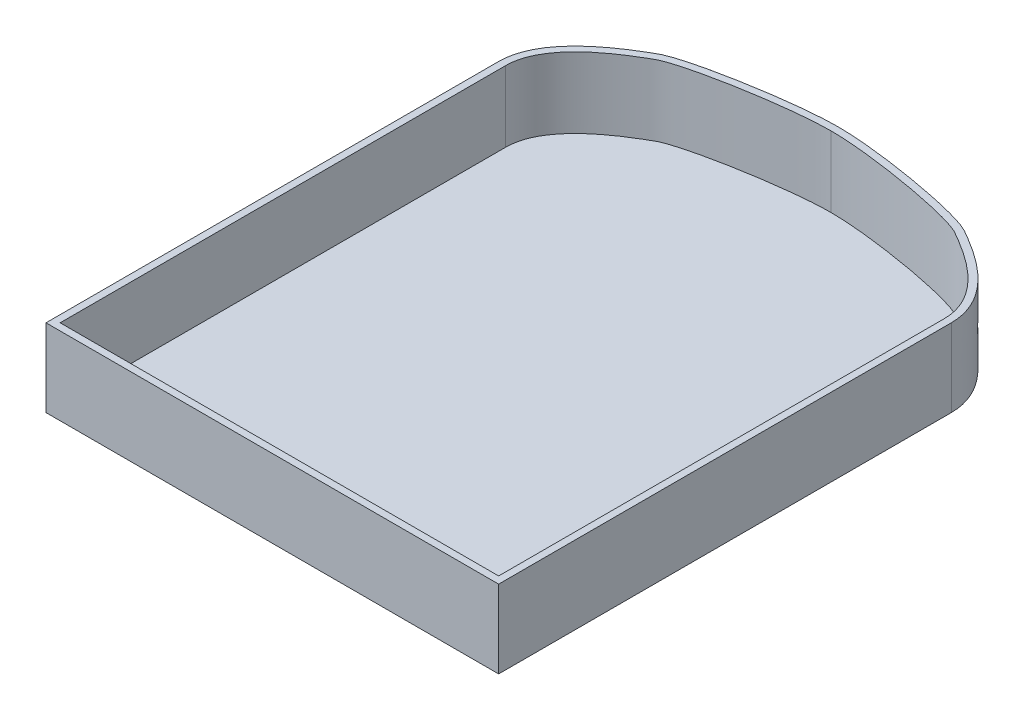
SolidWorks part; units mm, degrees
material "ABS"
ref_plane "Front Plane" through (0, 0, 0) normal (0, 0, 1) x (1, 0, 0)
ref_plane "Top Plane" through (0, 0, 0) normal (0, 1, 0) x (1, 0, 0)
ref_plane "Right Plane" through (0, 0, 0) normal (1, 0, 0) x (0, 0, -1)
sketch "Sketch1" plane through (0, 0, 0) normal (0, 1, 0) x (1, 0, 0)
  line L0 (-55, -80) -> (-55, 110) construction
  line L1 (80, 80) -> (80, -80)
  line L2 (-80, 80) -> (-80, -80)
  line L3 (-80, -80) -> (80, -80)
  line L4 (13.4478, 120) -> (-13.4478, 120) construction
  line L5 (-80, 80) -> (0, 0) construction
  line L6 (-80, -80) -> (0, 0) construction
  line L7 (140.1696, 222.6812) -> (-250.1696, -2.6812) construction
  line L8 (0, -80) -> (0, 120) construction
  spline S0 degree 3 poles (-80, 80) (-80, 95) (-57.9586, 108.2094) (-48.3668, 114.0523) (-15, 120) (0, 120) knots 0 0 0 0 0.16612 0.217304 0.51184 0.51184 0.51184 0.51184
  spline S1 degree 3 poles (80, 80) (80, 95) (57.9586, 108.2094) (48.3668, 114.0523) (15, 120) (0, 120) knots 0 0 0 0 0.16612 0.217304 0.51184 0.51184 0.51184 0.51184
  point P0 (0, 0)
  dimension "D3" = 25
  dimension "D6" = 113.1371
  dimension "D7" = 50
  dimension "D8" = 30
  dimension "D9" = 50
  dimension "D10" = 50
  dimension "D1" = 200
  dimension "D2" = 160
  dimension "D4" = 190
  dimension "D5" = 80
extrude "Boss-Extrude1" add sketch "Sketch1" along normal blind 2.5
sketch "Sketch3" plane through (0, 2.5, 0) normal (0, 1, 0) x (1, 0, 0)
  line L6 (-80, 80) -> (-80, -80)
  line L7 (-80, -80) -> (80, -80)
  line L8 (80, -80) -> (80, 80)
  line L9 (-80, 80) -> (-80, -80)
  line L10 (-80, -80) -> (80, -80)
  line L11 (80, -80) -> (80, 80)
  line L15 (-77.5, 80) -> (-77.5, -77.5)
  line L16 (-77.5, -77.5) -> (77.5, -77.5)
  line L17 (77.5, -77.5) -> (77.5, 80)
  line L18 (-77.5, 80) -> (-77.5, -77.5)
  line L19 (-77.5, -77.5) -> (77.5, -77.5)
  line L20 (77.5, -77.5) -> (77.5, 80)
  spline S4 degree 3 poles (-2906.9642, -618.3484) (562.0344, 187.5767) (-25.3353, 128.0822) (-71.1238, 100.1896) (-410.3236, -102.5425) (2892.7092, -269.8611) knots -1.229014 -1.229014 -1.229014 -1.229014 0.294536 0.34572 1.214364 1.214364 1.214364 1.214364 only from (0, 120) to (-80, 80)
  spline S5 degree 3 poles (-2892.5628, -269.8537) (410.3141, -102.5368) (71.1236, 100.1898) (25.3353, 128.0822) (-562.0328, 187.5765) (2906.9501, -618.3451) knots -0.702511 -0.702511 -0.702511 -0.702511 0.16612 0.217304 1.740852 1.740852 1.740852 1.740852 only from (80, 80) to (0, 120)
  spline S6 degree 3 poles (0, 120) (-15, 120) (-48.3668, 114.0523) (-57.9586, 108.2094) (-80, 95) (-80, 80) knots 0 0 0 0 0.294536 0.34572 0.51184 0.51184 0.51184 0.51184
  spline S7 degree 3 poles (80, 80) (80, 95) (57.9586, 108.2094) (48.3668, 114.0523) (15, 120) (0, 120) knots 0 0 0 0 0.16612 0.217304 0.51184 0.51184 0.51184 0.51184
  spline S10 degree 3 poles (649.7116, -2806.5157) (157.7684, 63.7543) (71.3763, 122.2374) (-7.815, 117.1661) (-9.7566, 116.9982) (-15.5689, 116.4083) (-19.4274, 115.902) (-27.1218, 114.7318) (-30.9575, 114.0669) (-36.6913, 112.933) (-38.5993, 112.5319) (-41.4543, 111.8826) (-42.4048, 111.6582) (-44.3029, 111.1884) (-45.2518, 110.9429) (-47.1348, 110.4247) (-48.0697, 110.1524) (-49.4545, 109.7092) (-49.9131, 109.5556) (-50.8213, 109.2304) (-51.271, 109.0591) (-52.1534, 108.6827) (-52.5848, 108.475) (-53.4295, 108.0238) (-53.8441, 107.7827) (-54.6696, 107.2932) (-55.0804, 107.0448) (-55.9027, 106.5489) (-56.3138, 106.3011) (-58.3647, 105.0521) (-59.9884, 104.0191) (-62.3722, 102.3669) (-63.1599, 101.7986) (-64.7045, 100.6307) (-65.4621, 100.0307) (-67.6842, 98.1751) (-69.0988, 96.8649) (-70.7492, 95.0983) (-71.0733, 94.7385) (-71.7083, 94.0043) (-72.0197, 93.6292) (-72.9258, 92.4878) (-73.4933, 91.7042) (-74.542, 90.0837) (-75.0233, 89.2467) (-75.8813, 87.5082) (-76.2591, 86.6008) (-97.5238, 22.5321) (214.1588, -109.4964) (2812.1935, -714.9326) knots -2.416048 -2.416048 -2.416048 -2.416048 0.0625 0.0625 0.125 0.125 0.25 0.25 0.375 0.375 0.4375 0.4375 0.46875 0.46875 0.5 0.5 0.53125 0.53125 0.546875 0.546875 0.5625 0.5625 0.578125 0.578125 0.59375 0.59375 0.609375 0.609375 0.625 0.625 0.6875 0.6875 0.71875 0.71875 0.75 0.75 0.8125 0.8125 0.828125 0.828125 0.84375 0.84375 0.875 0.875 0.90625 0.90625 0.9375 0.9375 3.090377 3.090377 3.090377 3.090377 only from (0, 117.5) to (-77.5, 80)
  spline S11 degree 3 poles (-2820.6032, -683.8631) (-228.4731, -110.921) (98.0659, 21.2534) (76.3991, 86.1764) (76.2263, 86.6364) (75.8509, 87.5394) (75.6485, 87.9819) (75.0021, 89.2855) (74.5187, 90.1226) (73.4656, 91.7439) (72.8957, 92.5281) (71.9857, 93.6707) (71.6726, 94.0466) (71.0345, 94.7821) (70.7089, 95.1424) (69.0523, 96.9103) (67.6355, 98.2186) (64.6735, 100.6864) (63.1276, 101.845) (60.7367, 103.4996) (59.9269, 104.0375) (58.2971, 105.0844) (57.4757, 105.5941) (56.2381, 106.3469) (55.8247, 106.5959) (54.9981, 107.0944) (54.585, 107.3441) (53.7547, 107.8347) (53.3375, 108.0757) (52.4873, 108.5236) (52.0531, 108.7283) (51.1672, 109.0998) (50.7166, 109.2693) (49.8075, 109.5916) (49.3489, 109.7439) (47.965, 110.1837) (47.0317, 110.4541) (45.153, 110.9689) (44.2064, 111.213) (42.3122, 111.6803) (41.3636, 111.9037) (38.5144, 112.5501) (36.6105, 112.9496) (30.8887, 114.0791) (27.0613, 114.7417) (19.3836, 115.9079) (15.5336, 116.4124) (9.7342, 117.0002) (7.797, 117.1675) (-71.3703, 122.2287) (-157.6885, 63.6621) (-646.7564, -2807.2372) knots -2.119433 -2.119433 -2.119433 -2.119433 0.0625 0.0625 0.078125 0.078125 0.09375 0.09375 0.125 0.125 0.15625 0.15625 0.171875 0.171875 0.1875 0.1875 0.25 0.25 0.3125 0.3125 0.34375 0.34375 0.375 0.375 0.390625 0.390625 0.40625 0.40625 0.421875 0.421875 0.4375 0.4375 0.453125 0.453125 0.46875 0.46875 0.5 0.5 0.53125 0.53125 0.5625 0.5625 0.625 0.625 0.75 0.75 0.875 0.875 0.9375 0.9375 3.421069 3.421069 3.421069 3.421069 only from (77.5, 80) to (0, 117.5)
  spline S12 degree 3 poles (0, 117.5) (-1.9658, 117.5) (-3.9194, 117.4156) (-7.815, 117.1661) (-9.7566, 116.9982) (-15.5689, 116.4083) (-19.4274, 115.902) (-27.1218, 114.7318) (-30.9575, 114.0669) (-36.6913, 112.933) (-38.5993, 112.5319) (-41.4543, 111.8826) (-42.4048, 111.6582) (-44.3029, 111.1884) (-45.2518, 110.9429) (-47.1348, 110.4247) (-48.0697, 110.1524) (-49.4545, 109.7092) (-49.9131, 109.5556) (-50.8213, 109.2304) (-51.271, 109.0591) (-52.1534, 108.6827) (-52.5848, 108.475) (-53.4295, 108.0238) (-53.8441, 107.7827) (-54.6696, 107.2932) (-55.0804, 107.0448) (-55.9027, 106.5489) (-56.3138, 106.3011) (-58.3647, 105.0521) (-59.9884, 104.0191) (-62.3722, 102.3669) (-63.1599, 101.7986) (-64.7045, 100.6307) (-65.4621, 100.0307) (-67.6842, 98.1751) (-69.0988, 96.8649) (-70.7492, 95.0983) (-71.0733, 94.7385) (-71.7083, 94.0043) (-72.0197, 93.6292) (-72.9258, 92.4878) (-73.4933, 91.7042) (-74.542, 90.0837) (-75.0233, 89.2467) (-75.8813, 87.5082) (-76.2591, 86.6008) (-77.1718, 83.8508) (-77.5, 81.9594) (-77.5, 80) knots 0 0 0 0 0.0625 0.0625 0.125 0.125 0.25 0.25 0.375 0.375 0.4375 0.4375 0.46875 0.46875 0.5 0.5 0.53125 0.53125 0.546875 0.546875 0.5625 0.5625 0.578125 0.578125 0.59375 0.59375 0.609375 0.609375 0.625 0.625 0.6875 0.6875 0.71875 0.71875 0.75 0.75 0.8125 0.8125 0.828125 0.828125 0.84375 0.84375 0.875 0.875 0.90625 0.90625 0.9375 0.9375 1 1 1 1
  spline S13 degree 3 poles (77.5, 80) (77.5, 81.9663) (77.1694, 83.8684) (76.3991, 86.1764) (76.2263, 86.6364) (75.8509, 87.5394) (75.6485, 87.9819) (75.0021, 89.2855) (74.5187, 90.1226) (73.4656, 91.7439) (72.8957, 92.5281) (71.9857, 93.6707) (71.6726, 94.0466) (71.0345, 94.7821) (70.7089, 95.1424) (69.0523, 96.9103) (67.6355, 98.2186) (64.6735, 100.6864) (63.1276, 101.845) (60.7367, 103.4996) (59.9269, 104.0375) (58.2971, 105.0844) (57.4757, 105.5941) (56.2381, 106.3469) (55.8247, 106.5959) (54.9981, 107.0944) (54.585, 107.3441) (53.7547, 107.8347) (53.3375, 108.0757) (52.4873, 108.5236) (52.0531, 108.7283) (51.1672, 109.0998) (50.7166, 109.2693) (49.8075, 109.5916) (49.3489, 109.7439) (47.965, 110.1837) (47.0317, 110.4541) (45.153, 110.9689) (44.2064, 111.213) (42.3122, 111.6803) (41.3636, 111.9037) (38.5144, 112.5501) (36.6105, 112.9496) (30.8887, 114.0791) (27.0613, 114.7417) (19.3836, 115.9079) (15.5336, 116.4124) (9.7342, 117.0002) (7.797, 117.1675) (3.9103, 117.416) (1.9612, 117.5) (0, 117.5) knots 0 0 0 0 0.0625 0.0625 0.078125 0.078125 0.09375 0.09375 0.125 0.125 0.15625 0.15625 0.171875 0.171875 0.1875 0.1875 0.25 0.25 0.3125 0.3125 0.34375 0.34375 0.375 0.375 0.390625 0.390625 0.40625 0.40625 0.421875 0.421875 0.4375 0.4375 0.453125 0.453125 0.46875 0.46875 0.5 0.5 0.53125 0.53125 0.5625 0.5625 0.625 0.625 0.75 0.75 0.875 0.875 0.9375 0.9375 1 1 1 1
  dimension "D1" = 0
  dimension "D2" = 2.5
extrude "Boss-Extrude2" add sketch "Sketch3" along normal blind 25
